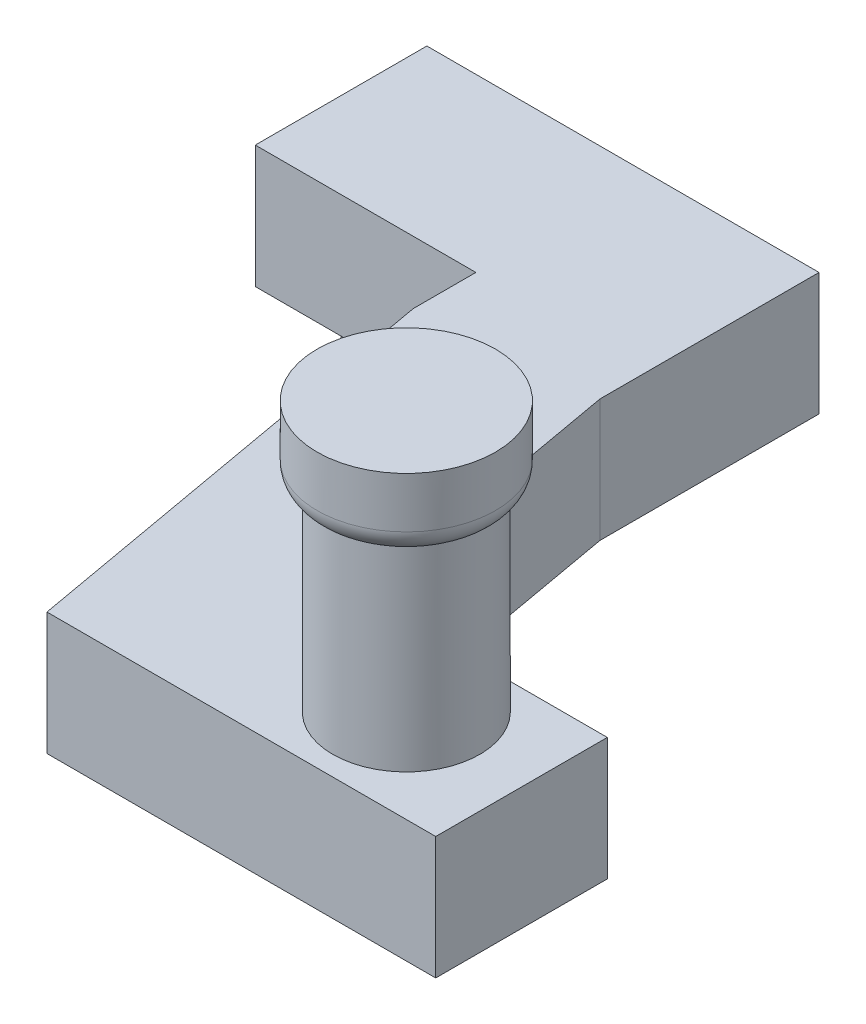
SolidWorks part; units mm, degrees
ref_plane "Front Plane" through (0, 0, 0) normal (0, 0, 1) x (1, 0, 0)
ref_plane "Top Plane" through (0, 0, 0) normal (0, 1, 0) x (1, 0, 0)
ref_plane "Right Plane" through (0, 0, 0) normal (1, 0, 0) x (0, 0, -1)
sketch "Sketch1" plane through (0, 0, 0) normal (0, 1, 0) x (1, 0, 0)
  line L0 (0, 0) -> (8, 0)
  line L1 (8, 0) -> (8, -4.4673)
  line L2 (8, -4.4673) -> (9.0546, -10.3739)
  line L3 (9.0546, -10.3739) -> (14.0546, -10.3739)
  line L4 (0, -3.5) -> (4.5, -3.5)
  line L5 (4.5, -3.5) -> (4.5, -4.7773)
  line L6 (4.5, -4.7773) -> (6.1242, -13.8739)
  line L7 (6.1242, -13.8739) -> (14.0546, -13.8739)
  line L8 (14.0546, -10.3739) -> (14.0546, -13.8739)
  line L9 (0, 0) -> (0, -3.5)
  dimension "D1" = 8
  dimension "D2" = 6
  dimension "D4" = 5
  dimension "D5" = 3.5
extrude "Boss-Extrude1" add sketch "Sketch1" along normal blind 2.5
sketch "Sketch2" plane through (0, 2.5, 0) normal (0, 1, 0) x (1, 0, 0)
  line L0 (14.0546, -10.3739) -> (9.0546, -10.3739) construction
  line L1 (14.0546, -13.8739) -> (14.0546, -10.3739) construction
  circle A0 centre (11.5546, -11.9739) radius 1.5
  dimension "D1" = 1.6
  dimension "D2" = 2.5
extrude "Boss-Extrude2" add sketch "Sketch2" along normal blind 4
sketch "Sketch3" plane through (0, 6.5, 0) normal (0, 1, 0) x (1, 0, 0)
  circle A0 centre (11.5546, -11.9739) radius 1.82
extrude "Boss-Extrude3" add sketch "Sketch3" along normal blind 1.5
fillet "Fillet2" radius 0.5 1 edges at (11.5546, 6.5, 13.7939)
sketch "Sketch4" plane through (0, 0, 0) normal (0, -1, 0) x (-1, 0, 0)
  circle A0 centre (-1.718, -1.4929) radius 1.4
extrude "Boss-Extrude4" add sketch "Sketch4" along normal blind 3.5
sketch "Sketch5" plane through (0, -3.5, 0) normal (0, -1, 0) x (1, 0, 0)
  circle A0 centre (1.7071, 1.4764) radius 1.7
extrude "Boss-Extrude5" add sketch "Sketch5" along normal blind 1
fillet "Fillet3" radius 0.5 1 edges at (1.7071, -3.5, -0.2236)
